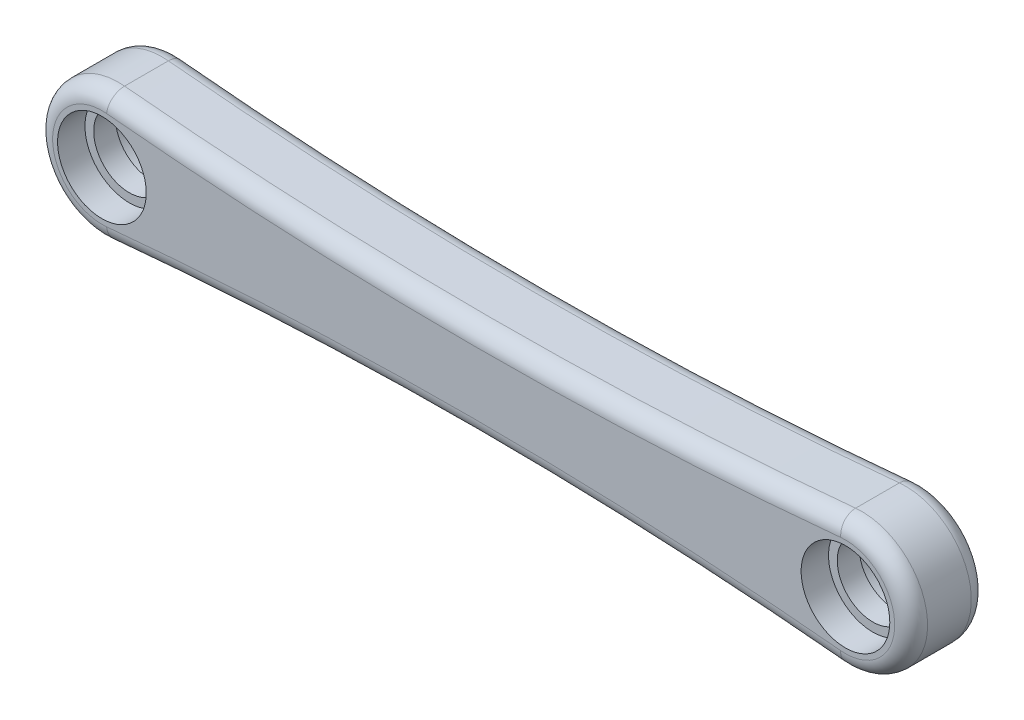
SolidWorks part; units mm, degrees
ref_plane "Front Plane" through (0, 0, 0) normal (0, 0, 1) x (1, 0, 0)
ref_plane "Top Plane" through (0, 0, 0) normal (0, 1, 0) x (1, 0, 0)
ref_plane "Right Plane" through (0, 0, 0) normal (1, 0, 0) x (0, 0, -1)
sketch "Sketch1" plane through (0, 0, 0) normal (0, 0, 1) x (1, 0, 0)
  line L0 (0, 0) -> (135.85, 0) construction
  line L1 (0, 0) -> (135.85, 0) construction
  line L2 (0, 12) -> (135.85, 12)
  line L3 (0, -12) -> (135.85, -12)
  arc A2 (0, 12) -> (0, -12) centre (0, 0) ccw
  arc A3 (135.85, -12) -> (135.85, 12) centre (135.85, 0) ccw
  circle A4 centre (0, 0) radius 8.1
  circle A5 centre (135.85, 0) radius 8.1
  point P3 (67.925, 0)
  dimension "D2" = 12
  dimension "D3" = 16.2
  dimension "D4" = 16.2
  dimension "D1" = 135.85
extrude "Boss-Extrude1" add sketch "Sketch1" along normal blind 5
sketch "Sketch2" plane through (0, 0, 5) normal (0, 0, 1) x (1, 0, 0)
  line L2 (0, -12) -> (135.85, -12)
  line L3 (135.85, 12) -> (0, 12)
  line L4 (0, -12) -> (135.85, -12)
  line L5 (135.85, 12) -> (0, 12)
  circle A0 centre (0, 0) radius 6.5
  circle A1 centre (135.85, 0) radius 6.5
  arc A2 (0, 12) -> (0, -12) centre (0, 0) ccw
  arc A3 (135.85, -12) -> (135.85, 12) centre (135.85, 0) ccw
  arc A4 (0, 12) -> (0, -12) centre (0, 0) ccw
  arc A5 (135.85, -12) -> (135.85, 12) centre (135.85, 0) ccw
  dimension "D2" = 13
  dimension "D3" = 13
  dimension "D1" = 0
extrude "Boss-Extrude2" add sketch "Sketch2" along normal blind 2
mirror "Mirror1" about plane through (0, 0, 7) normal (0, 0, 1) of bodies 102
sketch "Sketch4" plane through (0, 0, 0) normal (0, 0, -1) x (-1, 0, 0)
  line L0 (-135.85, 0) -> (0, 0) construction
  arc A0 (-134.7052, 11.9453) -> (-134.7052, -11.9453) centre (-135.85, 0) ccw
  arc A1 (-1.1448, -11.9453) -> (-1.1448, 11.9453) centre (0, 0) ccw
  arc A2 (-134.7052, 11.9453) -> (-1.1448, 11.9453) centre (-67.925, 708.7526) ccw
  arc A3 (-134.7052, -11.9453) -> (-1.1448, -11.9453) centre (-67.925, -708.7526) cw
  dimension "D1" = 24
  dimension "D2" = 24
  dimension "D3" = 700
  dimension "D4" = 135.85
extrude "Cut-Extrude1" cut sketch "Sketch4" against normal through all flip side to cut
fillet "Fillet2" radius 3 8 edges at (-12, 0, 14) (67.925, -8.7526, 14) (147.85, 0, 14) (-12, 0, 0) (67.925, -8.7526, 0) (147.85, 0, 0) (67.925, 8.7526, 14) (67.925, 8.7526, 0)
fillet "Fillet1" radius 2 rebuild error yes
